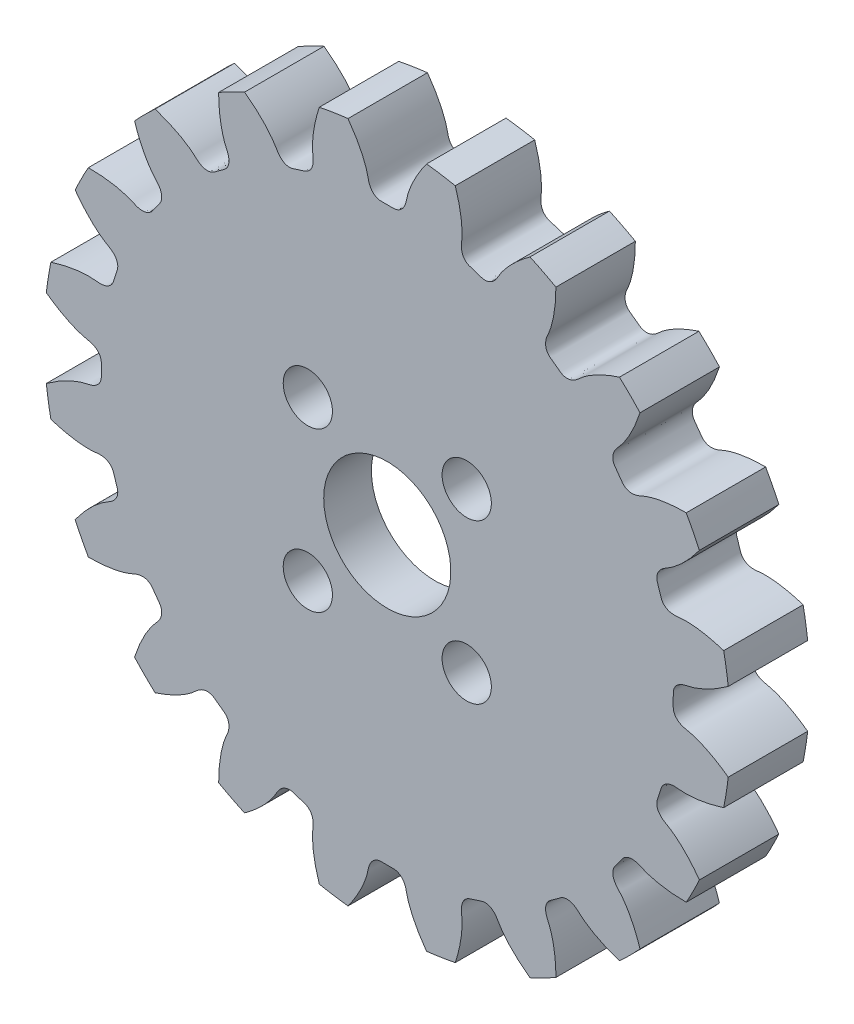
SolidWorks part; units mm, degrees
ref_plane "前视基准面" through (0, 0, 0) normal (0, 0, 1) x (1, 0, 0)
ref_plane "上视基准面" through (0, 0, 0) normal (0, 1, 0) x (1, 0, 0)
ref_plane "右视基准面" through (0, 0, 0) normal (1, 0, 0) x (0, 0, -1)
other "Configuration Table"
ref_axis "基准轴1" through (0, 0, 55) along (0, 0, -1)
sketch "SketchRevolveSpurGear1" plane through (0, 0, 0) normal (1, 0, 0) x (0, 0, -1)
  line L0 (0, 0) -> (1, 0) construction
  line L1 (-10, 0) -> (-10, 21.6)
  line L2 (-10, 21.6) -> (10, 21.6)
  line L3 (10, 21.6) -> (10, 0)
  line L4 (10, 0) -> (-10, 0)
revolve "SpurGear1" add sketch "SketchRevolveSpurGear1" angle 360 about L0
sketch "SketchToothSpurGear1" plane through (0, 0, 0) normal (0, 0, 1) x (1, 0, 0)
  arc A0 (21.5322, 2.5269) -> (21.5322, -2.5269) centre (0, 0) cw
  spline S0 degree 3 poles (21.5322, -2.5269) (21.3014, -2.3556) (20.9931, -2.145) (20.604, -1.9126) (20.3938, -1.795) (20.194, -1.6908) (20.0053, -1.5991) (19.8283, -1.5192) (19.6633, -1.4505) (19.511, -1.392) (19.3716, -1.3431) (19.2458, -1.303) (19.1338, -1.2708) (19.036, -1.2455) (18.8697, -1.2083) (18.7048, -1.1786) (18.5467, -1.1199) (18.4634, -1.0826) (18.3805, -1.037) (18.297, -0.98) (18.2128, -0.9069) (18.1301, -0.8111) (18.0562, -0.6863) (18.0071, -0.5384) (17.9872, -0.3051) (18.0091, 0) (17.9872, 0.3051) (18.0071, 0.5384) (18.0562, 0.6863) (18.1301, 0.8111) (18.2128, 0.9069) (18.297, 0.98) (18.3805, 1.037) (18.4634, 1.0826) (18.5467, 1.1199) (18.7048, 1.1786) (18.8697, 1.2083) (19.036, 1.2455) (19.1338, 1.2708) (19.2458, 1.303) (19.3716, 1.3431) (19.511, 1.392) (19.6633, 1.4505) (19.8283, 1.5192) (20.0053, 1.5991) (20.194, 1.6908) (20.3938, 1.795) (20.604, 1.9126) (20.9931, 2.145) (21.3014, 2.3556) (21.5322, 2.5269) knots 0 0 0 0 0.091955 0.119295 0.144978 0.169005 0.191374 0.212086 0.231141 0.248539 0.26428 0.278365 0.290792 0.301562 0.310676 0.345325 0.354891 0.364542 0.374515 0.385131 0.396818 0.410091 0.425426 0.442936 0.459429 0.5 0.540571 0.557064 0.574574 0.589909 0.603182 0.614869 0.625485 0.635458 0.645109 0.654675 0.689324 0.698438 0.709208 0.721635 0.73572 0.751461 0.768859 0.787914 0.808626 0.830995 0.855022 0.880705 0.908045 1 1 1 1
extrude "ToothExtrudeCutSpurGear1" cut sketch "SketchToothSpurGear1" against normal blind 10 and the other way blind 10
pattern_circular "PatternSpurGear1" count 20 every 18 about axis through (0, 0, 55) along (0, 0, -1) of "ToothExtrudeCutSpurGear1"
sketch "BoreRevolveSketch" plane through (0, 0, 0) normal (1, 0, 0) x (0, 0, -1)
  line L0 (0, 0) -> (1, 0) construction
  line L1 (-10, 0) -> (10, 0)
  line L2 (10, 0) -> (10, 5)
  line L3 (10, 5) -> (-10, 5)
  line L4 (-10, 5) -> (-10, 0)
  dimension "TaperSide1" = 5
  dimension "TaperSide2" = 5
revolve "BoreRevolveCut" cut sketch "BoreRevolveSketch" angle 360 about L0
sketch "AuxiliarySketchSpurGear1" plane through (0, 0, 0) normal (0, 0, 1) x (1, 0, 0)
  circle A0 centre (0, 0) radius 20 construction
  circle A1 centre (0, 0) radius 18.7939 construction
  circle A2 centre (0, 0) radius 18.9161 construction
  circle A3 centre (0, 0) radius 21.6 construction
  circle A4 centre (0, 0) radius 18 construction
  dimension "PitchDiameter" = 40
  dimension "BaseDiameter" = 37.5877
  dimension "FormDiameter" = 37.8322
  dimension "MajorDiameter" = 43.2
  dimension "MinorDiameter" = 36
sketch "草图5" plane through (0, 0, 10) normal (0, 0, 1) x (1, 0, 0)
  circle A0 centre (0, 0) radius 5
extrude "凸台-拉伸1" add sketch "草图5" against normal blind 10
sketch "草图6" plane through (0, 0, -10) normal (0, 0, -1) x (-1, 0, 0)
  circle A0 centre (0, 0) radius 21.6
extrude "切除-拉伸3" cut sketch "草图6" against normal blind 15
sketch "草图8" plane through (0, 0, 5) normal (0, 0, -1) x (-1, 0, 0)
  circle A0 centre (0, 0) radius 10.5
  dimension "D1" = 21
extrude "切除-拉伸4" cut sketch "草图8" against normal blind 2
sketch "草图9" plane through (0, 0, 7) normal (0, 0, -1) x (-1, 0, 0)
  line L1 (-5, -5) -> (5, -5)
  line L2 (-5, -5) -> (-5, 5)
  line L3 (-5, 5) -> (5, 5)
  line L4 (5, -5) -> (5, 5)
  line L5 (-5, -5) -> (5, 5) construction
  line L6 (-5, 5) -> (5, -5) construction
  circle A0 centre (0, 0) radius 4
  circle A2 centre (-5, 5) radius 1.55
  circle A3 centre (5, 5) radius 1.55
  circle A4 centre (5, -5) radius 1.55
  circle A5 centre (-5, -5) radius 1.55
  point P17 (0, 0)
  dimension "D1" = 8
  dimension "D4" = 3.1
  dimension "D2" = 10
  dimension "D3" = 10
  dimension "D5" = 4
extrude "切除-拉伸6" cut sketch "草图9" against normal through all contours A0 | A2 | A5 | A4 | A3 region at (0, 0, 7)
sketch "草图10" plane through (0, 0, 5) normal (0, 0, -1) x (-1, 0, 0)
  circle A0 centre (0, 0) radius 21.6
